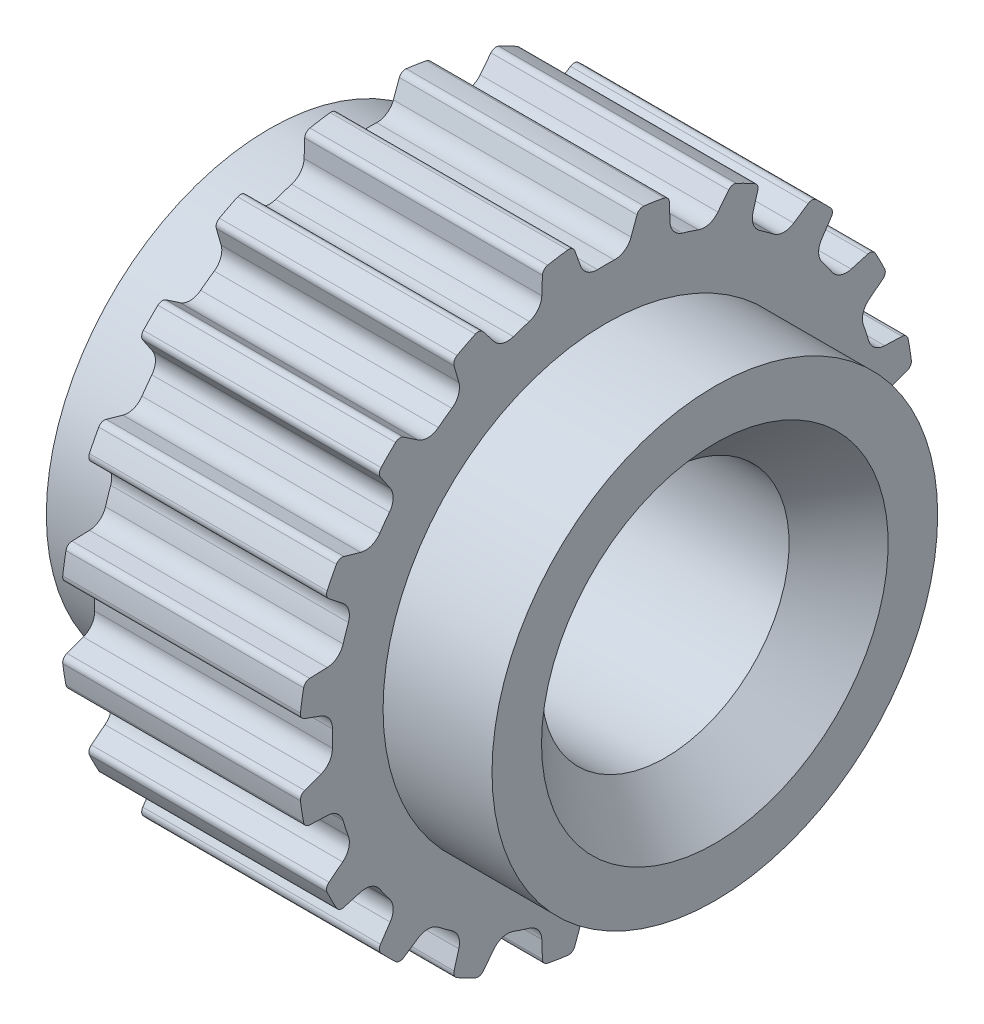
SolidWorks part; units mm, degrees
ref_plane "前视基准面" through (0, 0, 0) normal (0, 0, 1) x (1, 0, 0)
ref_plane "上视基准面" through (0, 0, 0) normal (0, 1, 0) x (1, 0, 0)
ref_plane "右视基准面" through (0, 0, 0) normal (1, 0, 0) x (0, 0, -1)
sketch "草图1" plane through (0, 0, 0) normal (0, 0, 1) x (1, 0, 0)
  line L0 (0, 0) -> (64.8368, 0) construction
  line L1 (0, 2.5) -> (0, 6.216)
  line L2 (0, 6.216) -> (4.8, 6.216)
  line L3 (4.8, 6.216) -> (4.8, 4.5)
  line L4 (4.8, 4.5) -> (7, 4.5)
  line L5 (7, 4.5) -> (7, 2.5)
  line L6 (7, 2.5) -> (0, 2.5)
  dimension "L" = 7
  dimension "B" = 4.8
  dimension "d" = 5
  dimension "d1" = 9
  dimension "da" = 12.432
revolve "旋转1" add sketch "草图1" angle 360 about L0
sketch "草图7" plane through (0, 0, 0) normal (-1, 0, 0) x (0, 0, 1)
  circle A0 centre (0, 0) radius 2.5 construction
  circle A1 centre (0, 0) radius 2.5
  circle A2 centre (0, 0) radius 4.5 construction
  circle A3 centre (0, 0) radius 4.5
extrude "凸台-拉伸1" add sketch "草图7" along normal blind 2
chamfer "倒角1" distance 1 angle 45 2 edges at (7, 0, 2.5) (-2, 0, 2.5)
ref_axis "基准轴1" through (-0.35, 0, 0) along (1, 0, 0)
sketch "草图6" plane through (0, 0, 0) normal (1, 0, 0) x (0, 0, -1)
  line L0 (0, 0) -> (0, 16.0158) construction
  line L1 (0.6289, 6.0839) -> (0.5086, 5.7535)
  line L2 (0.8959, 6.1511) -> (1.394, 7.5196)
  line L3 (-0.8959, 6.1511) -> (-1.394, 7.5196)
  line L4 (-0.6289, 6.0839) -> (-0.5086, 5.7535)
  circle A0 centre (0, 0) radius 6.216 construction
  arc A1 (0.169, 5.5234) -> (-0.169, 5.5234) centre (0, 0) ccw
  arc A2 (0.7671, 6.1685) -> (0.8959, 6.1511) centre (0, 0) cw
  arc A3 (0.5086, 5.7535) -> (0.169, 5.5234) centre (0.1797, 5.8733) cw
  arc A4 (0.6289, 6.0839) -> (0.7671, 6.1685) centre (0.7511, 6.0395) cw
  arc A5 (1.394, 7.5196) -> (-1.394, 7.5196) centre (0, 0) ccw
  arc A6 (-0.7671, 6.1685) -> (-0.8959, 6.1511) centre (0, 0) ccw
  arc A7 (-0.6289, 6.0839) -> (-0.7671, 6.1685) centre (-0.7511, 6.0395) ccw
  arc A8 (-0.5086, 5.7535) -> (-0.169, 5.5234) centre (-0.1797, 5.8733) ccw
  point P8 (0, 15.3258)
  point P14 (0.664, 6.1804)
  point P16 (0.42, 5.51)
  dimension "D1" = 5.526
  dimension "ra" = 0.13
  dimension "rf" = 0.35
  dimension "D3" = 1.4563
  dimension "D4" = 0.13
  dimension "bw" = 0.84
  dimension "angle" = 40
  dimension "hg" = 0.69
extrude "切除-拉伸2" cut sketch "草图6" along normal up to next
pattern_circular "阵列(圆周)3" count 20 over 360 about axis through (-0.35, 0, 0) along (1, 0, 0) of "切除-拉伸2"
equation "\"D4@草图6\"= \"ra@草图6\""
equation "\"D1@草图6\" = \"da@草图1\" / 2 - \"hg@草图6\" "
